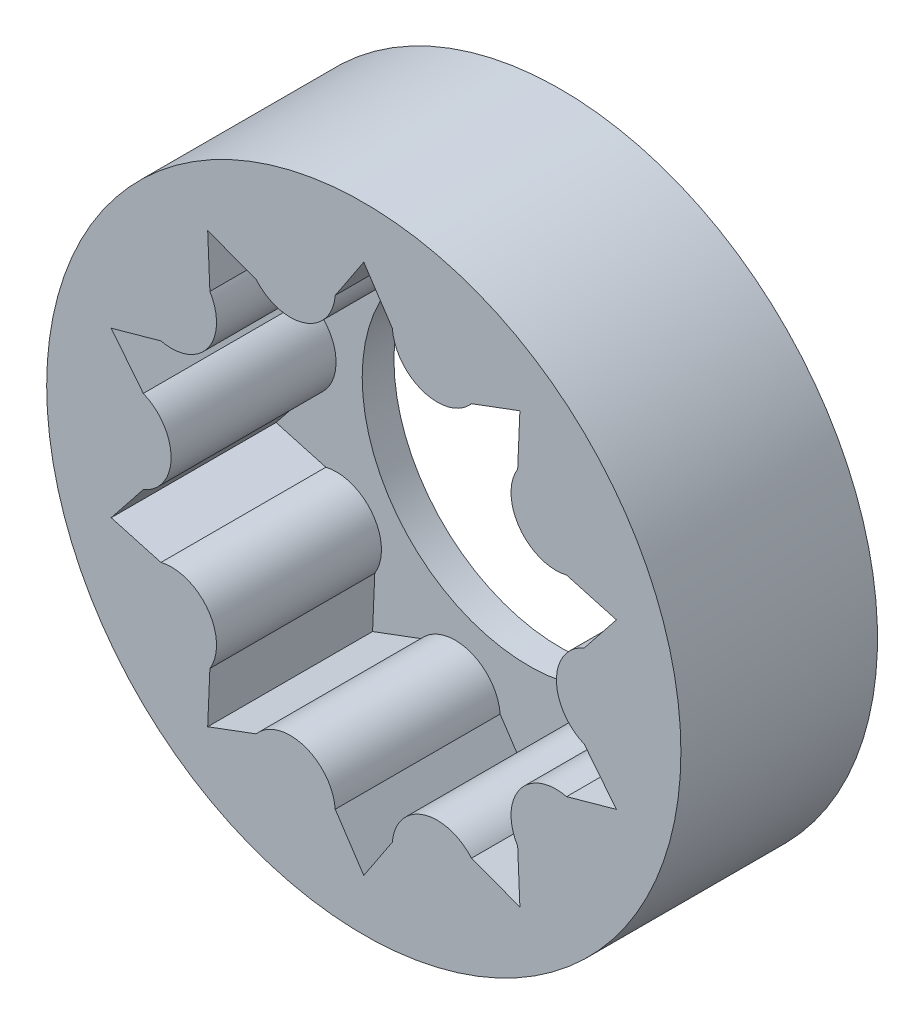
SolidWorks part; units mm, degrees
ref_plane "Front Plane" through (0, 0, 0) normal (0, 0, 1) x (1, 0, 0)
ref_plane "Top Plane" through (0, 0, 0) normal (0, 1, 0) x (1, 0, 0)
ref_plane "Right Plane" through (0, 0, 0) normal (1, 0, 0) x (0, 0, -1)
sketch "Sketch1" plane through (0, 0, 0) normal (0, 0, 1) x (1, 0, 0)
  line L0 (0, 0) -> (0, 16.75)
  line L1 (0, 0) -> (9.8454, 13.551)
  line L2 (0, 16.75) -> (1.8002, 14.035)
  line L3 (6.7932, 12.4127) -> (9.8454, 13.551)
  line L4 (0, 0) -> (0, 20)
  line L5 (0, 0) -> (11.7557, 16.1803)
  circle A0 centre (0, 0) radius 12.15
  circle A1 centre (0, 0) radius 16.75
  circle A2 centre (0, 0) radius 14.15 construction
  arc A3 (1.8002, 14.035) -> (6.7932, 12.4127) centre (4.6325, 14.2573) ccw
  circle A4 centre (0, 0) radius 20
  dimension "D1" = 24.3
  dimension "D3" = 2.6
  dimension "D6" = 40
  dimension "D4" = 36
  dimension "D5" = 5.25
extrude "Boss-Extrude1" add sketch "Sketch1" along normal blind 10.4 contours L2 A3 L3 A1 | L5 A4 L4 A1 region at (4.5856, 14.113, 0) region at (5.5998, 17.2344, 0)
ref_axis "Axis1" through (0, 0, -0.52) along (0, 0, 1)
pattern_circular "CirPattern1" count 10 over 360 about axis through (0, 0, -0.52) along (0, 0, 1) of "Boss-Extrude1"
sketch "Sketch2" plane through (0, 0, 0) normal (0, 0, -1) x (-1, 0, 0)
  circle A0 centre (0, 0) radius 10.5
  circle A1 centre (0, 0) radius 20
  dimension "D1" = 21
extrude "Boss-Extrude2" add sketch "Sketch2" along normal blind 2
